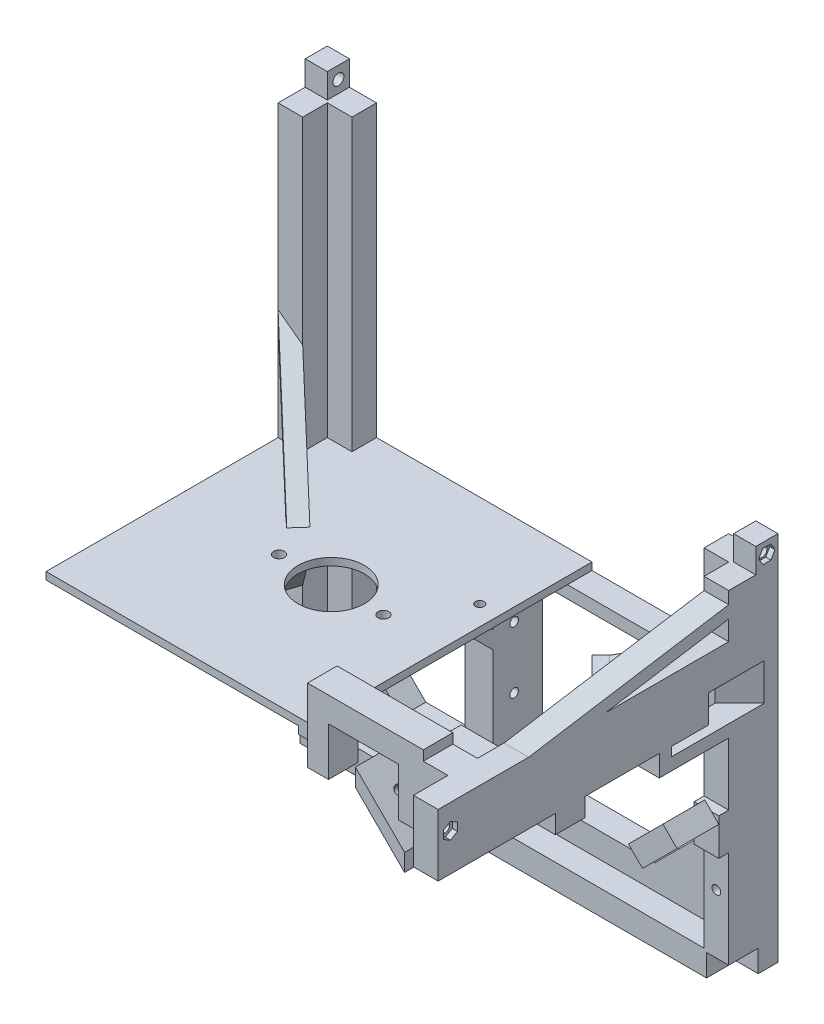
SolidWorks part; units mm, degrees
ref_plane "Front Plane" through (0, 0, 0) normal (0, 0, 1) x (1, 0, 0)
ref_plane "Top Plane" through (0, 0, 0) normal (0, 1, 0) x (1, 0, 0)
ref_plane "Right Plane" through (0, 0, 0) normal (1, 0, 0) x (0, 0, -1)
sketch "Sketch1" plane through (0, 0, 0) normal (0, 0, 1) x (1, 0, 0)
  line L0 (0, 0) -> (-91.5, 0)
  line L1 (-91.5, 0) -> (-91.5, 220.775)
  line L2 (-91.5, 220.775) -> (-71.5, 220.775)
  line L3 (-71.5, 220.775) -> (-71.5, 40)
  line L4 (-51.5, 20) -> (0, 20)
  line L5 (0, 20) -> (0, 0) construction
  line L6 (0, 20) -> (51.5, 20)
  line L7 (71.5, 40) -> (71.5, 140.775)
  line L8 (71.5, 140.775) -> (91.5, 140.775)
  line L9 (91.5, 140.775) -> (91.5, 0)
  line L10 (91.5, 0) -> (0, 0)
  line L11 (-71.5, 40) -> (-51.5, 20)
  line L12 (71.5, 40) -> (51.5, 20)
  dimension "D1" = 220.775
  dimension "D2" = 20
  dimension "D3" = 91.5
  dimension "D4" = 80
  dimension "D5" = 45
  dimension "D6" = 20
  dimension "D7" = 20
  dimension "D8" = 45
extrude "Boss-Extrude1" add sketch "Sketch1" along normal blind 10
sketch "Sketch2" plane through (0, 0, 10) normal (0, 0, 1) x (1, 0, 0)
  line L0 (-81.5, 220.775) -> (-91.5, 220.775)
  line L1 (-71.5, 220.775) -> (-91.5, 220.775) construction
  line L2 (-91.5, 220.775) -> (-91.5, 0)
  line L3 (-91.5, 0) -> (91.5, 0)
  line L4 (91.5, 0) -> (91.5, 140.775)
  line L5 (91.5, 140.775) -> (81.5, 140.775)
  line L6 (91.5, 140.775) -> (71.5, 140.775) construction
  line L7 (81.5, 140.775) -> (81.5, 10)
  line L8 (81.5, 10) -> (-81.5, 10)
  line L9 (-81.5, 10) -> (-81.5, 220.775)
  dimension "D1" = 10
extrude "Boss-Extrude2" add sketch "Sketch2" along normal blind 10
sketch "Sketch3" plane through (0, 220.775, 0) normal (0, 1, 0) x (1, 0, 0)
  line L1 (-91.5, 0) -> (-82.5, 0)
  line L2 (-91.5, 0) -> (-91.5, -9)
  line L3 (-91.5, -9) -> (-82.5, -9)
  line L4 (-82.5, 0) -> (-82.5, -9)
  dimension "D1" = 9
sketch "Sketch5" plane through (0, 140.775, 0) normal (0, 1, 0) x (1, 0, 0)
  line L1 (91.5, 0) -> (82.5, 0)
  line L2 (91.5, 0) -> (91.5, -9)
  line L3 (91.5, -9) -> (82.5, -9)
  line L4 (82.5, 0) -> (82.5, -9)
  dimension "D1" = 9
extrude "Boss-Extrude3" add sketch "Sketch3" along normal blind 10
extrude "Boss-Extrude4" add sketch "Sketch5" along normal blind 10
sketch "Sketch6" plane through (-91.5, 0, 0) normal (-1, 0, 0) x (0, 0, 1)
  line L0 (0, 230.775) -> (9, 230.775) construction
  line L1 (9, 230.775) -> (9, 220.775) construction
  circle A0 centre (4.5, 225.775) radius 2.25
  point P4 (4.5, 230.775)
  point P7 (9, 225.775)
  dimension "D1" = 4.5
extrude "Cut-Extrude1" cut sketch "Sketch6" against normal up to surface (9 mm away) up to face at (-82.5, 225.775, 4.5)
sketch "Sketch7" plane through (91.5, 0, 0) normal (1, 0, 0) x (0, 0, -1)
  line L0 (-9, 150.775) -> (0, 150.775) construction
  line L1 (-9, 150.775) -> (-9, 140.775) construction
  circle A0 centre (-4.5, 145.775) radius 2.25
  point P4 (-4.5, 150.775)
  point P7 (-9, 145.775)
  dimension "D1" = 4.5
extrude "Cut-Extrude2" cut sketch "Sketch7" against normal up to surface (9 mm away) up to face at (82.5, 145.775, 4.5)
sketch "Sketch8" plane through (0, 0, 0) normal (0, 0, -1) x (-1, 0, 0)
  line L0 (91.5, 0) -> (-91.5, 0) construction
  line L1 (91.5, 230.775) -> (91.5, 0) construction
  line L2 (-91.5, 0) -> (-91.5, 150.775) construction
  circle A0 centre (86.5, 33) radius 1.75
  circle A1 centre (-86.5, 33) radius 1.75
  dimension "D1" = 3.5
  dimension "D4" = 5
  dimension "D2" = 33
  dimension "D3" = 5
extrude "Cut-Extrude3" cut sketch "Sketch8" against normal through all
sketch "Sketch9" plane through (0, 0, 20) normal (0, 0, 1) x (1, 0, 0)
  line L0 (82.5, 140.775) -> (91.5, 140.775) construction
  line L8 (81.5, 122.765) -> (91.5, 122.765)
  line L9 (81.5, 122.765) -> (81.5, 97.565)
  line L10 (81.5, 97.565) -> (91.5, 97.565)
  line L11 (91.5, 122.765) -> (91.5, 97.565)
  line L12 (81.5, 140.775) -> (81.5, 10) construction
  line L13 (91.5, 0) -> (91.5, 140.775) construction
  dimension "D1" = 18.01
  dimension "D2" = 25.2
extrude "Boss-Extrude5" add sketch "Sketch9" along normal blind 118
ref_plane "Plane1" through (0, 107.915, 0) normal (0, -1, 0) x (-1, 0, 0)
sketch "Sketch16" plane through (0, 107.915, 0) normal (0, -1, 0) x (-1, 0, 0)
  line L0 (-81.5, -38.1924) -> (-81.5, -19.8076)
  line L1 (-81.5, -138) -> (-81.5, -20) construction
  line L2 (-81.5, -19.8076) -> (-63.4688, -37.8388)
  line L3 (-63.4688, -37.8388) -> (-72.6612, -47.0312)
  line L4 (-72.6612, -47.0312) -> (-81.5, -38.1924)
  point P4 (-81.5, -29)
  dimension "D1" = 45
  dimension "D2" = 13
  dimension "D3" = 9
  dimension "D4" = 25.5
extrude "Boss-Extrude8" add sketch "Sketch16" against normal blind 5
sketch "Sketch17" plane through (12.815, 0, -12.815) normal (-0.7071, 0, 0.7071) x (0.7071, 0, 0.7071)
  line L5 (84.6353, 112.915) -> (84.6353, 107.915) construction
  line L6 (68.6353, 107.915) -> (84.6353, 107.915)
  line L7 (68.6353, 107.915) -> (68.6353, 93.915)
  line L8 (68.6353, 93.915) -> (84.6353, 93.915)
  line L9 (84.6353, 107.915) -> (84.6353, 93.915)
  line L10 (84.6353, 107.915) -> (71.6353, 107.915) construction
  dimension "D1" = 14
  dimension "D2" = 16
extrude "Cut-Extrude8" cut sketch "Sketch17" against normal up to surface (26.6421 mm away)
ref_plane "Plane2" through (0, 98.065, 0) normal (0, 1, 0) x (1, 0, 0)
sketch "Sketch20" plane through (0, 98.065, 0) normal (0, 1, 0) x (1, 0, 0)
  line L0 (-50.2132, -60.9183) -> (-45.7132, -60.9183) construction
  line L3 (-50.2132, -60.9183) -> (-54.7132, -60.9183) construction
  line L11 (-91.5, -20) -> (-54.7132, -52.9183)
  line L12 (-54.7132, -66.9183) -> (-45.7132, -66.9183)
  line L13 (-54.7132, -66.9183) -> (-54.7132, -52.9183)
  line L15 (-45.7132, -66.9183) -> (-45.7132, -52.0234)
  line L16 (-91.5, -20) -> (-81.5, -20)
  line L17 (-81.5, -20) -> (-45.7132, -52.0234)
  line L18 (-50.2132, -60.9183) -> (-50.2132, -66.9183) construction
  circle A4 centre (-50.2132, -60.9183) radius 3.01 construction
  dimension "D2" = 4.5
  dimension "D4" = 6
  dimension "D6" = 35.7868
  dimension "D1" = 6.02
  dimension "D5" = 46.9183
  dimension "D3" = 8
extrude "Boss-Extrude10" add sketch "Sketch20" along normal blind 5
sketch "Sketch21" plane through (-50.626, 0, 56.5756) normal (-0.6668, 0, 0.7452) x (0.7452, 0, 0.6668)
  line L6 (-5.4846, 98.065) -> (-54.8494, 48.7002)
  line L7 (-54.8494, 98.065) -> (-54.8494, 0) construction
  line L8 (-54.8494, 48.7002) -> (-54.8494, 53.7002)
  line L9 (-54.8494, 53.7002) -> (-10.4846, 98.065)
  line L10 (-54.8494, 98.065) -> (-5.4846, 98.065) construction
  line L11 (-10.4846, 98.065) -> (-5.4846, 98.065)
  line L12 (-54.8494, 148.065) -> (-9.8494, 103.065)
  line L13 (-54.8494, 220.775) -> (-54.8494, 103.065) construction
  line L14 (-54.8494, 103.065) -> (-5.4846, 103.065) construction
  line L15 (-9.8494, 103.065) -> (-14.8494, 103.065)
  line L16 (-14.8494, 103.065) -> (-54.8494, 143.065)
  line L17 (-54.8494, 143.065) -> (-54.8494, 148.065)
  dimension "D1" = 5
  dimension "D2" = 5
  dimension "D3" = 40
extrude "Boss-Extrude11" add sketch "Sketch21" against normal up to surface (6.6684 mm away) up to face at (-63.6066, 100.565, 36.0117)
sketch "Sketch22" plane through (0, 97.565, 0) normal (0, -1, 0) x (1, 0, 0)
  line L0 (-91.5, 20) -> (91.5, 20) construction
  line L6 (91.5, 78.38) -> (41.2468, 78.38)
  line L8 (91.5, 90.38) -> (41.2468, 90.38)
  line L9 (41.2468, 78.38) -> (41.2468, 90.38)
  line L10 (47.2468, 84.38) -> (47.2468, 78.38) construction
  line L11 (47.2468, 84.38) -> (41.2468, 84.38) construction
  line L13 (91.5, 138) -> (91.5, 28.1924) construction
  line L14 (91.5, 90.38) -> (91.5, 78.38)
  dimension "D1" = 64.38
  dimension "D2" = 50.2532
  dimension "D4" = 6
extrude "Boss-Extrude12" add sketch "Sketch22" along normal blind 7.5
sketch "Sketch23" plane through (0, 0, 90.38) normal (0, 0, 1) x (1, 0, 0)
  line L0 (41.2468, 90.065) -> (41.2468, 97.565) construction
  line L1 (41.2468, 90.065) -> (59.2468, 90.065)
  line L2 (41.2468, 90.065) -> (41.2468, 97.565)
  line L3 (41.2468, 97.565) -> (59.2468, 97.565)
  line L4 (59.2468, 90.065) -> (59.2468, 97.565)
  dimension "D1" = 18
sketch "Sketch25" plane through (91.5, 0, 0) normal (1, 0, 0) x (0, 0, -1)
  line L7 (-20, 135.775) -> (-101.211, 122.765)
  line L8 (-20, 122.765) -> (-20, 140.775) construction
  line L9 (-138, 122.765) -> (-20, 122.765) construction
  line L10 (-101.211, 122.765) -> (-70, 122.765)
  line L11 (-70, 122.765) -> (-20, 130.775)
  line L12 (-20, 130.775) -> (-20, 135.775)
  line L13 (-20, 140.775) -> (-9, 140.775) construction
  dimension "D1" = 5
  dimension "D2" = 50
  dimension "D3" = 5
extrude "Boss-Extrude13" add sketch "Sketch25" against normal up to surface (10 mm away) up to face at (81.5, 98.5144, 42.946)
sketch "Sketch26" plane through (81.5, 0, 0) normal (-1, 0, 0) x (0, 0, 1)
  line L1 (124.03, 122.765) -> (112.03, 122.765)
  line L2 (124.03, 122.765) -> (124.03, 97.065)
  line L3 (124.03, 97.065) -> (112.03, 97.065)
  line L4 (112.03, 122.765) -> (112.03, 97.065)
  line L5 (138, 97.565) -> (90.38, 97.565) construction
  line L6 (138, 122.765) -> (101.211, 122.765) construction
  line L7 (20, 48.7002) -> (20, 0) construction
  dimension "D1" = 92.03
  dimension "D2" = 0.5
  dimension "D3" = 12
extrude "Boss-Extrude14" add sketch "Sketch26" along normal blind 20
sketch "Sketch28" plane through (0, 122.765, 0) normal (0, 1, 0) x (1, 0, 0)
  line L0 (61.5, -112.03) -> (81.5, -112.03) construction
  line L1 (71.5, -112.03) -> (24.5, -112.03)
  line L2 (71.5, -112.03) -> (71.5, -124.03)
  line L3 (71.5, -124.03) -> (24.5, -124.03)
  line L4 (24.5, -112.03) -> (24.5, -124.03)
  line L5 (91.5, -138) -> (81.5, -138) construction
  line L6 (61.5, -124.03) -> (81.5, -124.03) construction
  dimension "D1" = 47
extrude "Boss-Extrude15" add sketch "Sketch28" along normal blind 4 and the other way blind 6.1
sketch "Sketch29" plane through (0, 0, 124.03) normal (0, 0, 1) x (1, 0, 0)
  line L0 (61.5, 97.065) -> (81.5, 97.065) construction
  line L1 (24.5, 116.665) -> (33, 116.665)
  line L2 (24.5, 116.665) -> (24.5, 97.065)
  line L3 (24.5, 97.065) -> (33, 97.065)
  line L4 (33, 116.665) -> (33, 97.065)
  dimension "D1" = 8.5
extrude "Boss-Extrude16" add sketch "Sketch29" against normal up to surface (12 mm away) up to face at (62.1667, 113.7872, 112.03)
sketch "Sketch30" plane through (0, 97.065, 0) normal (0, -1, 0) x (1, 0, 0)
  line L0 (29.75, 117.76) -> (64.75, 117.76) construction
  line L1 (33, 124.03) -> (61.5, 124.03) construction
  line L2 (33, 112.03) -> (24.5, 112.03) construction
  circle A10 centre (29.75, 117.76) radius 1.75
  circle A11 centre (64.75, 117.76) radius 1.75
  point P6 (47.25, 124.03)
  point P7 (47.25, 117.76)
  dimension "D1" = 3.5
  dimension "D2" = 35
  dimension "D3" = 5.73
extrude "Cut-Extrude11" cut sketch "Sketch30" against normal blind 10
ref_plane "Plane3" through (0, 53.95, 0) normal (0, -1, 0) x (-1, 0, 0)
sketch "Sketch38" plane through (12.815, 0, -12.815) normal (-0.7071, 0, 0.7071) x (0.7071, 0, 0.7071)
  line L1 (64.589, 107.915) -> (84.589, 107.915)
  line L2 (64.589, 107.915) -> (64.589, 94.605)
  line L3 (64.589, 94.605) -> (84.589, 94.605)
  line L4 (84.589, 107.915) -> (84.589, 94.605)
  line L5 (84.589, 90.065) -> (84.589, 97.565) construction
  dimension "D1" = 20
  dimension "D2" = 13.31
extrude "Boss-Extrude19" add sketch "Sketch38" against normal blind 5.1
sketch "Sketch39" plane through (91.5, 0, 0) normal (1, 0, 0) x (0, 0, -1)
  line L0 (-138, 97.565) -> (-138, 122.765) construction
  line L1 (-138, 122.765) -> (-101.211, 122.765) construction
  circle A0 centre (-133, 112.765) radius 1.75
  dimension "D2" = 3.5
  dimension "D1" = 5
  dimension "D3" = 10
ref_plane "Plane4" through (-24.94, 0, 0) normal (-1, 0, 0) x (0, 0, 1)
sketch "Sketch41" plane through (0, 10, 0) normal (0, 1, 0) x (1, 0, 0)
  line L0 (-15.67, -20) -> (-15.67, 0)
  line L1 (-91.5, 0) -> (-91.5, -9) construction
  line L3 (81.5, -20) -> (-81.5, -20) construction
  line L4 (51.5, 0) -> (-51.5, 0) construction
  line L5 (-15.67, 0) -> (-4.15, 0)
  line L6 (-4.15, 0) -> (-4.15, -20)
  line L7 (-4.15, -20) -> (-15.67, -20)
  point P6 (-9.91, 0)
  dimension "D1" = 81.59
  dimension "D2" = 11.52
extrude "Boss-Extrude21" add sketch "Sketch41" along normal blind 90.06 separate body
ref_plane "Plane5" through (-9.91, 0, 0) normal (-1, 0, 0) x (0, 0, 1)
sketch "Sketch45" plane through (0, 0, 0) normal (0, -1, 0) x (1, 0, 0)
  line L0 (-22.11, 20) -> (-22.11, 38.01) construction
  line L1 (-91.5, 20) -> (91.5, 20) construction
  line L2 (-91.5, 20) -> (-91.5, 0) construction
  line L4 (-12.11, 20) -> (-32.11, 20)
  line L5 (-12.11, 20) -> (-12.11, 48.01)
  line L6 (-12.11, 48.01) -> (-32.11, 48.01)
  line L7 (-32.11, 20) -> (-32.11, 48.01)
  point P10 (-22.11, 48.01)
  dimension "D1" = 69.39
  dimension "D2" = 18.01
  dimension "D3" = 20
  dimension "D4" = 10
extrude "Boss-Extrude25" add sketch "Sketch45" against normal blind 34.49
sketch "Sketch52" plane through (-15.67, 0, 0) normal (-1, 0, 0) x (0, 0, 1)
  line L0 (20, 100.06) -> (68, 100.06)
  line L1 (68, 100.06) -> (68, 95.06)
  line L2 (68, 95.06) -> (43, 95.06)
  line L3 (20, 95.06) -> (20, 100.06)
  line L4 (43, 95.06) -> (20, 72.06)
  line L5 (20, 72.06) -> (20, 79.1311)
  line L6 (20, 100.06) -> (20, 10) construction
  line L7 (20, 79.1311) -> (35.9289, 95.06)
  line L8 (35.9289, 95.06) -> (20, 95.06)
  line L10 (20, 98.065) -> (20, 53.7002) construction
  dimension "D1" = 5
  dimension "D2" = 48
  dimension "D3" = 5
  dimension "D4" = 25
  dimension "D5" = 45
extrude "Boss-Extrude26" add sketch "Sketch52" against normal up to surface (11.52 mm away) up to face at (-4.15, 55.03, 10)
sketch "Sketch53" plane through (0, 95.06, 0) normal (0, -1, 0) x (1, 0, 0)
  circle A5 centre (-7.7868, 60.9183) radius 3.0099 construction
  circle A6 centre (-7.7868, 60.9183) radius 2.2
  dimension "D1" = 4.4
extrude "Cut-Extrude20" cut sketch "Sketch53" against normal up to surface (5 mm away) up to face at (-9.91, 100.06, 34)
sketch "Sketch47" plane through (0, 0, 20) normal (0, 0, -1) x (-1, 0, 0)
  line L0 (39.9206, 38.6883) -> (4.4536, 3.2213)
  line L1 (4.4536, 3.2213) -> (-9.9508, 17.6257)
  line L2 (-9.9508, 17.6257) -> (25.5162, 53.0927)
  line L3 (25.5162, 53.0927) -> (39.9206, 38.6883)
  line L4 (32.11, 34.49) -> (15.67, 34.49) construction
  line L5 (35.2258, 26.9225) -> (9.9055, 1.6022)
  line L6 (9.9055, 1.6022) -> (23.1824, -11.6747)
  line L7 (23.1824, -11.6747) -> (48.5027, 13.6456)
  line L8 (48.5027, 13.6456) -> (35.2258, 26.9225)
  dimension "D1" = 45
  dimension "D2" = 20.3708
  dimension "D3" = 5
extrude "Cut-Extrude17" cut sketch "Sketch47" along normal offset from surface (23.01 mm away) 5 from surface at -28.01 up to face at (-23.89, 22.245, 20) starting at face at (-22.11, 17.245, 48.01)
sketch "Sketch54" plane through (-46.1793, 0, 51.6063) normal (0.6668, 0, -0.7452) x (-0.7452, 0, -0.6668)
  line L0 (47.3974, 103.065) -> (14.8494, 103.065) construction
  line L1 (1.6137, 103.065) -> (6.6137, 103.065)
  line L2 (1.6137, 103.065) -> (1.6137, 98.065)
  line L3 (1.6137, 98.065) -> (6.6137, 98.065)
  line L4 (6.6137, 103.065) -> (6.6137, 98.065)
  line L6 (47.3974, 98.065) -> (10.4846, 98.065) construction
  line L7 (46.6137, 40) -> (46.6137, 220.775) construction
  dimension "D1" = 5
  dimension "D2" = 40
extrude "Boss-Extrude27" add sketch "Sketch54" along normal up to surface (53.1432 mm away)
sketch "Sketch55" plane through (0, 0, 0) normal (0, 0, -1) x (-1, 0, 0)
  line L0 (-71.5, 140.775) -> (-71.5, 40) construction
  line L1 (4.15, 100.06) -> (-71.5, 100.06)
  line L2 (4.15, 100.06) -> (4.15, 95.06)
  line L3 (4.15, 95.06) -> (-71.5, 95.06)
  line L4 (-71.5, 100.06) -> (-71.5, 95.06)
  dimension "D1" = 5
extrude "Boss-Extrude28" add sketch "Sketch55" against normal up to surface (10 mm away) up to face at (49.8857, 54.5071, 10)
sketch "Sketch56" plane through (0, 95.06, 0) normal (0, -1, 0) x (1, 0, 0)
  line L0 (-13.65, 43) -> (-13.65, 69)
  line L1 (-4.15, 43) -> (-15.67, 43) construction
  line L3 (-13.65, 69) -> (-16.67, 69)
  line L4 (-16.67, 69) -> (-16.67, 43)
  line L5 (-16.67, 43) -> (-13.65, 43)
  line L6 (-4.15, 68) -> (-15.67, 68) construction
  line L7 (-15.67, 43) -> (-15.67, 68) construction
  line L8 (-4.15, 68) -> (-4.15, 43) construction
  dimension "D1" = 1
  dimension "D2" = 1
  dimension "D3" = 9.5
extrude "Cut-Extrude21" cut sketch "Sketch56" against normal up to surface (5 mm away) up to face at (-5.5868, 100.06, 60.9183)
extrude "Cut-Extrude22" cut sketch "Sketch23" against normal blind 2.2
chamfer "Chamfer1" distance 0.5 angle 75 2 edges at (64.75, 97.065, 116.01) (29.75, 97.065, 116.01)
ref_plane "Plane6" through (0, 56.04, 0) normal (0, -1, 0) x (-1, 0, 0)
sketch "Sketch60" plane through (0, 56.04, 0) normal (0, -1, 0) x (-1, 0, 0)
  line L0 (-81.5, -78.38) -> (-81.5, -38.1924) construction
  line L1 (-91.5, -20) -> (-81.5, -20)
  line L2 (-91.5, -20) -> (-91.5, -24)
  line L3 (-91.5, -24) -> (-81.5, -24)
  line L4 (-81.5, -20) -> (-81.5, -24)
  dimension "D1" = 4
extrude "Boss-Extrude31" add sketch "Sketch60" along normal blind 7.5 and the other way blind 7.5
sketch "Sketch61" plane through (0, 0, 24) normal (0, 0, 1) x (1, 0, 0)
  line L0 (85.2775, 66.7625) -> (71.2775, 52.7625)
  line L4 (77.5, 46.54) -> (91.5, 60.54)
  line L5 (91.5, 63.54) -> (91.5, 48.54) construction
  line L6 (91.5, 60.54) -> (85.2775, 66.7625)
  line L7 (91.5, 63.54) -> (81.5, 63.54) construction
  line L8 (71.2775, 52.7625) -> (77.5, 46.54)
  line L10 (91.5, 48.54) -> (81.5, 48.54) construction
  line L11 (81.5, 48.54) -> (91.5, 48.54) construction
  dimension "D1" = 45
  dimension "D2" = 12
  dimension "D3" = 2
  dimension "D4" = 8.8
extrude "Boss-Extrude32" add sketch "Sketch61" along normal blind 17
extrude "Cut-Extrude25" cut sketch "Sketch39" against normal up to surface (10 mm away) up to face at (81.5, 110.165, 131.015)
sketch "Sketch63" plane through (16.4212, 0, -16.4212) normal (0.7071, 0, -0.7071) x (-0.7071, 0, -0.7071)
  line L1 (-64.589, 107.915) -> (-64.589, 94.605) construction
  line L2 (-64.589, 94.605) -> (-84.589, 94.605) construction
  circle A3 centre (-75.849, 102.51) radius 2.25
  dimension "D1" = 4.5
  dimension "D2" = 11.26
  dimension "D3" = 7.905
extrude "Cut-Extrude26" cut sketch "Sketch63" against normal blind 10
sketch "Sketch64" plane through (0, 103.065, 0) normal (0, 1, 0) x (1, 0, 0)
  line L13 (-91.5, -114.2195) -> (-91.5, -14.5)
  line L16 (-91.5, -114.2195) -> (16, -114.2195)
  line L17 (16, 0) -> (16, -114.2195)
  line L18 (-91.5, -20) -> (-91.5, -9) construction
  line L19 (-91.5, -14.5) -> (-81.5, -15)
  line L20 (-81.5, -20) -> (-81.5, -10) construction
  line L21 (-81.5, -15) -> (-81.5, 0)
  line L22 (-71.5, 0) -> (-82.5, 0) construction
  line L23 (-81.5, 0) -> (16, 0)
  circle A4 centre (-29, -60.9183) radius 13.5
extrude "Boss-Extrude33" add sketch "Sketch64" against normal blind 3 contours A4 | L16 L17 L23 L21 L19 L13
sketch "Sketch65" plane through (0, 95.06, 0) normal (0, -1, 0) x (1, 0, 0)
  circle A0 centre (-7.7868, 60.9183) radius 2.2 construction
  circle A1 centre (-7.7868, 60.9183) radius 2.2
  circle A5 centre (-50.2132, 60.9183) radius 3.2639 construction
  circle A6 centre (-50.2132, 60.9183) radius 2.2
  dimension "D1" = 4.4
extrude "Cut-Extrude27" cut sketch "Sketch65" against normal up to surface (8.005 mm away) up to face at (-57.6055, 103.065, 45.8559)
sketch "Sketch66" plane through (0, 100.065, 0) normal (0, -1, 0) x (1, 0, 0)
  line L0 (-12.11, 20) -> (91.5, 20) construction
  line L2 (16, 0) -> (16, 114.2195) construction
  circle A0 centre (8, 37.59) radius 1.75
  dimension "D1" = 3.5
  dimension "D2" = 17.59
  dimension "D3" = 8
extrude "Cut-Extrude28" cut sketch "Sketch66" against normal up to surface (3 mm away) up to face at (-7.7868, 103.065, 63.1183)
sketch "Sketch69" plane through (0, 0, 0) normal (0, 0, -1) x (-1, 0, 0)
  line L0 (91.5, 0) -> (-91.5, 0) construction
  line L1 (-88.1454, 30.15) -> (-84.8546, 30.15)
  line L2 (-84.8546, 30.15) -> (-83.2091, 33)
  line L3 (-83.2091, 33) -> (-84.8546, 35.85)
  line L4 (-84.8546, 35.85) -> (-88.1454, 35.85)
  line L5 (-88.1454, 35.85) -> (-89.7909, 33)
  line L6 (-89.7909, 33) -> (-88.1454, 30.15)
  line L8 (88.1454, 30.15) -> (89.7909, 33)
  line L9 (89.7909, 33) -> (88.1454, 35.85)
  line L10 (88.1454, 35.85) -> (84.8546, 35.85)
  line L11 (84.8546, 35.85) -> (83.2091, 33)
  line L12 (83.2091, 33) -> (84.8546, 30.15)
  line L13 (84.8546, 30.15) -> (88.1454, 30.15)
  circle A0 centre (-86.5, 33) radius 2.85 construction
  circle A1 centre (86.5, 33) radius 2.85 construction
  dimension "D1" = 5.7
extrude "Cut-Extrude30" cut sketch "Sketch69" against normal blind 2.1
sketch "Sketch70" plane through (91.5, 0, 0) normal (1, 0, 0) x (0, 0, -1)
  line L0 (-9, 150.775) -> (0, 150.775) construction
  line L1 (-2.8546, 142.925) -> (-1.2091, 145.775)
  line L2 (-1.2091, 145.775) -> (-2.8546, 148.625)
  line L3 (-2.8546, 148.625) -> (-6.1454, 148.625)
  line L4 (-6.1454, 148.625) -> (-7.7909, 145.775)
  line L5 (-7.7909, 145.775) -> (-6.1454, 142.925)
  line L6 (-6.1454, 142.925) -> (-2.8546, 142.925)
  circle A0 centre (-4.5, 145.775) radius 2.85 construction
  dimension "D1" = 5.7
extrude "Cut-Extrude31" cut sketch "Sketch70" against normal blind 2.1
sketch "Sketch71" plane through (-91.5, 0, 0) normal (-1, 0, 0) x (0, 0, 1)
  line L0 (0, 230.775) -> (9, 230.775) construction
  line L1 (6.1454, 222.925) -> (7.7909, 225.775)
  line L2 (7.7909, 225.775) -> (6.1454, 228.625)
  line L3 (6.1454, 228.625) -> (2.8546, 228.625)
  line L4 (2.8546, 228.625) -> (1.2091, 225.775)
  line L5 (1.2091, 225.775) -> (2.8546, 222.925)
  line L6 (2.8546, 222.925) -> (6.1454, 222.925)
  circle A0 centre (4.5, 225.775) radius 2.85 construction
  dimension "D1" = 5.7
extrude "Cut-Extrude32" cut sketch "Sketch71" against normal blind 2.1
sketch "Sketch72" plane through (0, 0, 20) normal (0, 0, 1) x (1, 0, 0)
  line L1 (91.5, 0) -> (82.5, 0)
  line L2 (91.5, 0) -> (91.5, 9)
  line L3 (91.5, 9) -> (82.5, 9)
  line L4 (82.5, 0) -> (82.5, 9)
  line L5 (-91.5, 0) -> (-82.5, 0)
  line L6 (-91.5, 0) -> (-91.5, 9)
  line L7 (-91.5, 9) -> (-82.5, 9)
  line L8 (-82.5, 0) -> (-82.5, 9)
  dimension "D1" = 9
  dimension "D2" = 9
extrude "Cut-Extrude33" cut sketch "Sketch72" against normal blind 12
sketch "Sketch74" plane through (0, 9, 0) normal (0, -1, 0) x (1, 0, 0)
  line L1 (-82.5, 20) -> (-91.5, 20) construction
  line L2 (91.5, 20) -> (82.5, 20) construction
  circle A0 centre (-87, 14) radius 1.8
  circle A1 centre (87, 14) radius 1.8
  point P6 (-87, 20)
  point P10 (87, 20)
  dimension "D1" = 3.6
  dimension "D2" = 6
extrude "Cut-Extrude35" cut sketch "Sketch74" against normal blind 10
chamfer "Chamfer2" distance 0.5 angle 75 2 edges at (87, 9, 12.2) (-87, 9, 12.2)
sketch "Sketch76" plane through (0, 0, 112.03) normal (0, 0, -1) x (-1, 0, 0)
  line L0 (-24.5, 97.065) -> (-11, 97.065)
  line L1 (-11, 97.065) -> (-11, 100.065)
  line L2 (-11, 100.065) -> (-16, 100.065)
  line L3 (-16, 100.065) -> (-16, 102.065)
  line L4 (-16, 102.065) -> (-24.5, 102.065)
  line L5 (-24.5, 97.065) -> (-24.5, 126.765) construction
  line L6 (-24.5, 102.065) -> (-24.5, 97.065)
  line L7 (-9.75, 100.065) -> (-6.25, 100.065) construction
  dimension "D1" = 5
extrude "Boss-Extrude34" add sketch "Sketch76" against normal up to surface (2.1895 mm away) up to face at (-37.75, 101.565, 114.2195)
sketch "Sketch77" plane through (91.5, 0, 0) normal (1, 0, 0) x (0, 0, -1)
  line L0 (-138, 97.565) -> (-138, 122.765) construction
  line L1 (-130.15, 114.4104) -> (-133, 116.0559)
  line L2 (-133, 116.0559) -> (-135.85, 114.4104)
  line L3 (-135.85, 114.4104) -> (-135.85, 111.1196)
  line L4 (-135.85, 111.1196) -> (-133, 109.4741)
  line L5 (-133, 109.4741) -> (-130.15, 111.1196)
  line L6 (-130.15, 111.1196) -> (-130.15, 114.4104)
  circle A0 centre (-133, 112.765) radius 2.85 construction
  circle A1 centre (-133, 112.765) radius 1.75 construction
  circle A2 centre (-133, 112.765) radius 1.75 construction
  dimension "D1" = 5.7
extrude "Cut-Extrude36" cut sketch "Sketch77" against normal blind 2.1 contours L4 L5 L6 L1 L2 L3
sketch "Sketch81" plane through (91.5, 0, 0) normal (1, 0, 0) x (0, 0, -1)
  line L0 (-20, 93.915) -> (-43.1924, 93.915)
  line L1 (-43.1924, 93.915) -> (-43.1924, 97.565)
  line L2 (-78.38, 97.565) -> (-28.1924, 97.565) construction
  line L3 (-43.1924, 97.565) -> (-48.1924, 97.565)
  line L4 (-48.1924, 97.565) -> (-48.1924, 88.915)
  line L5 (-48.1924, 88.915) -> (-20, 88.915)
  line L6 (-20, 63.54) -> (-20, 93.915) construction
  line L7 (-20, 88.915) -> (-20, 93.915)
  dimension "D1" = 5
  dimension "D2" = 15
extrude "Boss-Extrude36" add sketch "Sketch81" against normal up to surface (10 mm away) up to face at (81.5, 114.515, 133)
sketch "Sketch82" plane through (16.4212, 0, -16.4212) normal (0.7071, 0, -0.7071) x (-0.7071, 0, -0.7071)
  line L1 (-84.6353, 107.915) -> (-68.6353, 107.915)
  line L2 (-84.6353, 107.915) -> (-84.6353, 108.915)
  line L3 (-84.6353, 108.915) -> (-68.6353, 108.915)
  line L4 (-68.6353, 107.915) -> (-68.6353, 108.915)
  dimension "D1" = 1
extrude "Cut-Extrude37" cut sketch "Sketch82" against normal up to surface (21.5421 mm away)
sketch "Sketch83" plane through (12.815, 0, -12.815) normal (-0.7071, 0, 0.7071) x (0.7071, 0, 0.7071)
  line L8 (71.6353, 112.915) -> (71.6353, 107.915)
  line L9 (71.6353, 107.915) -> (64.589, 107.915)
  line L10 (64.589, 107.915) -> (64.589, 94.605)
  line L11 (64.589, 94.605) -> (84.589, 94.605)
  line L12 (84.589, 94.605) -> (84.589, 107.915)
  line L13 (84.589, 107.915) -> (84.6353, 107.915)
  line L14 (84.6353, 107.915) -> (84.6353, 112.915)
  line L15 (84.6353, 112.915) -> (71.6353, 112.915)
  line L16 (71.6353, 112.915) -> (71.6353, 107.915)
  line L17 (71.6353, 107.915) -> (64.589, 107.915)
  line L18 (64.589, 107.915) -> (64.589, 94.605)
  line L19 (64.589, 94.605) -> (84.589, 94.605)
  line L20 (84.589, 94.605) -> (84.589, 107.915)
  line L22 (84.6353, 107.915) -> (84.6353, 112.915)
  line L23 (84.6353, 112.915) -> (71.6353, 112.915)
  line L24 (84.589, 107.915) -> (84.6353, 107.915)
  circle A3 centre (75.849, 102.51) radius 2.25 construction
  circle A4 centre (75.849, 102.51) radius 2.25
  dimension "D1" = 0
extrude "Boss-Extrude37" add sketch "Sketch83" along normal blind 6.8
sketch "Sketch85" plane through (0, 0, 90.38) normal (0, 0, 1) x (1, 0, 0)
  line L0 (64.3223, 97.565) -> (81.5, 122.765)
  line L1 (81.5, 97.565) -> (59.2468, 97.565) construction
  line L2 (81.5, 122.765) -> (81.5, 97.565) construction
  line L3 (81.5, 122.765) -> (81.5, 113.8879)
  line L4 (81.5, 113.8879) -> (70.3734, 97.565)
  line L5 (70.3734, 97.565) -> (64.3223, 97.565)
  dimension "D1" = 5
extrude "Boss-Extrude38" add sketch "Sketch85" against normal up to surface (12 mm away) up to face at (69.3987, 94.565, 78.38)
sketch "Sketch86" plane through (50.6538, 0, 50.6538) normal (-0.7071, 0, -0.7071) x (-0.7071, 0, 0.7071)
  line L0 (-16.3231, 112.915) -> (-43.6231, 117.915)
  line L1 (-11.3231, 112.915) -> (-43.6231, 112.915) construction
  line L2 (-43.6231, 117.915) -> (-43.6231, 112.915)
  line L3 (-43.6231, 112.915) -> (-16.3231, 112.915)
  line L4 (-11.3231, 112.915) -> (-11.3231, 107.915) construction
  dimension "D1" = 5
  dimension "D2" = 5
extrude "Boss-Extrude39" add sketch "Sketch86" against normal up to surface (13 mm away) up to face at (75.2067, 109.915, 44.4856)
sketch "Sketch87" plane through (0, 100.065, 0) normal (0, -1, 0) x (1, 0, 0)
  line L0 (-29, 89.6551) -> (-57.7368, 60.9183)
  line L1 (-57.7368, 60.9183) -> (-29, 32.1815)
  line L2 (-29, 32.1815) -> (-0.2632, 60.9183)
  line L3 (-0.2632, 60.9183) -> (-29, 89.6551)
  line L4 (-57.7368, 60.9183) -> (-0.2632, 60.9183) construction
  line L5 (-29, 89.6551) -> (-29, 32.1815) construction
  circle A0 centre (-29, 60.9183) radius 13.5 construction
  circle A1 centre (-29, 60.9183) radius 13.5 construction
  point P7 (-29, 60.9183)
  dimension "D1" = 40.64
sketch "Sketch88" plane through (0, 100.065, 0) normal (0, -1, 0) x (1, 0, 0)
  line L0 (-51.7368, 66.9183) -> (-29, 89.6551)
  line L1 (-29, 89.6551) -> (-57.7368, 60.9183) construction
  line L2 (-45.7132, 66.9183) -> (-54.7132, 66.9183) construction
  line L3 (-29, 89.6551) -> (-7.3449, 68)
  line L4 (-0.2632, 60.9183) -> (-29, 89.6551) construction
  line L5 (-4.15, 68) -> (-13.65, 68) construction
  line L6 (-7.3449, 68) -> (-13.65, 68)
  line L7 (-13.65, 68) -> (-29, 83.35)
  line L8 (-29, 89.6551) -> (-29, 32.1815) construction
  line L9 (-29, 83.35) -> (-45.4317, 66.9183)
  line L10 (-54.7132, 66.9183) -> (-45.7132, 66.9183) construction
  line L11 (-45.4317, 66.9183) -> (-51.7368, 66.9183)
  line L12 (-49.2132, 52.3946) -> (-29, 40.1815)
  line L13 (-29, 40.1815) -> (-8.7868, 52.3946)
  line L14 (-29, 32.1815) -> (-0.2632, 60.9183) construction
  line L16 (-8.7868, 52.3946) -> (-29, 32.1815)
  line L17 (-29, 32.1815) -> (-49.2132, 52.3946)
  line L18 (-57.7368, 60.9183) -> (-29, 32.1815) construction
  line L19 (-45.7132, 66.9183) -> (-45.7132, 52.0234) construction
  dimension "D1" = 8
  dimension "D2" = 3.5
extrude "Boss-Extrude41" add sketch "Sketch88" along normal up to surface (2 mm away) up to face at (-71.3579, 98.065, 33.5497)
sketch "Sketch89" plane through (-13.65, 0, 0) normal (-1, 0, 0) x (0, 0, 1)
  line L0 (68, 100.06) -> (49.4562, 100.06) construction
  line L1 (68, 93.06) -> (43, 93.06)
  line L2 (68, 93.06) -> (68, 98.06)
  line L3 (68, 98.06) -> (43, 98.06)
  line L4 (43, 93.06) -> (43, 98.06)
  line L5 (68, 98.065) -> (68, 100.06) construction
  line L7 (43, 100.06) -> (43, 95.06) construction
  dimension "D1" = 2
  dimension "D2" = 5
extrude "Cut-Extrude38" cut sketch "Sketch89" against normal up to surface (9.5 mm away)
sketch "Sketch90" plane through (0, 90.065, 0) normal (0, -1, 0) x (1, 0, 0)
  line L0 (91.5, 78.38) -> (41.2468, 78.38) construction
  line L1 (41.2468, 78.38) -> (41.2468, 88.18) construction
  circle A0 centre (47.2468, 85.03) radius 2.2
  dimension "D3" = 4.4
  dimension "D1" = 6.65
  dimension "D2" = 6
extrude "Cut-Extrude39" cut sketch "Sketch90" against normal blind 5
sketch "Sketch91" plane through (0, 0, 41) normal (0, 0, 1) x (1, 0, 0)
  line L0 (71.7795, 52.2605) -> (85.7795, 66.2605)
  line L1 (71.2775, 52.7625) -> (77.5, 46.54) construction
  line L2 (91.5, 60.54) -> (85.2775, 66.7625) construction
  line L3 (85.2775, 66.7625) -> (71.2775, 52.7625) construction
  line L4 (85.7795, 66.2605) -> (82.5223, 69.5177)
  line L5 (82.5223, 69.5177) -> (68.5223, 55.5177)
  line L6 (68.5223, 55.5177) -> (71.7795, 52.2605)
  dimension "D1" = 0.71
extrude "Cut-Extrude40" cut sketch "Sketch91" against normal up to surface (17 mm away) up to face at (85.2775, 64.6142, 24)
sketch "Sketch93" plane through (15.48, -15.48, 0) normal (0.7071, -0.7071, 0) x (0, 0, -1)
  line L0 (-24, 93.3664) -> (-24, 107.5085) construction
  line L2 (-41, 87.7095) -> (-24, 87.7095) construction
  circle A0 centre (-32.29, 94.9895) radius 1.75
  dimension "D1" = 3.5
  dimension "D2" = 8.29
  dimension "D3" = 7.28
extrude "Cut-Extrude41" cut sketch "Sketch93" against normal up to surface (8.09 mm away) up to face at (79.9462, 60.4272, 29.6667)
sketch "Sketch94" plane through (-4.1517, -4.1517, 0) normal (-0.7071, -0.7071, 0) x (0, 0, 1)
  line L0 (48.01, 11.2548) -> (48.01, 39.5391) construction
  line L2 (25, 11.2548) -> (48.01, 11.2548) construction
  circle A0 centre (38.66, 32.6448) radius 1.75
  dimension "D1" = 3.5
  dimension "D2" = 9.35
  dimension "D3" = 21.39
extrude "Cut-Extrude42" cut sketch "Sketch94" against normal up to surface (5 mm away) up to face at (-22.11, 20.8777, 36.505)
sketch "Sketch95" plane through (-4.15, 0, 0) normal (1, 0, 0) x (0, 0, -1)
  line L0 (0, 0) -> (0, 150.775) construction
  line L1 (-8, 0) -> (-20, 0) construction
  circle A0 centre (-11.48, 52.66) radius 1.75
  circle A1 centre (-11.48, 77.66) radius 1.75
  dimension "D2" = 3.5
  dimension "D4" = 25
  dimension "D1" = 11.48
  dimension "D3" = 52.66
extrude "Cut-Extrude43" cut sketch "Sketch95" against normal up to surface (11.52 mm away) up to face at (-15.67, 89.7504, 25.3096)
